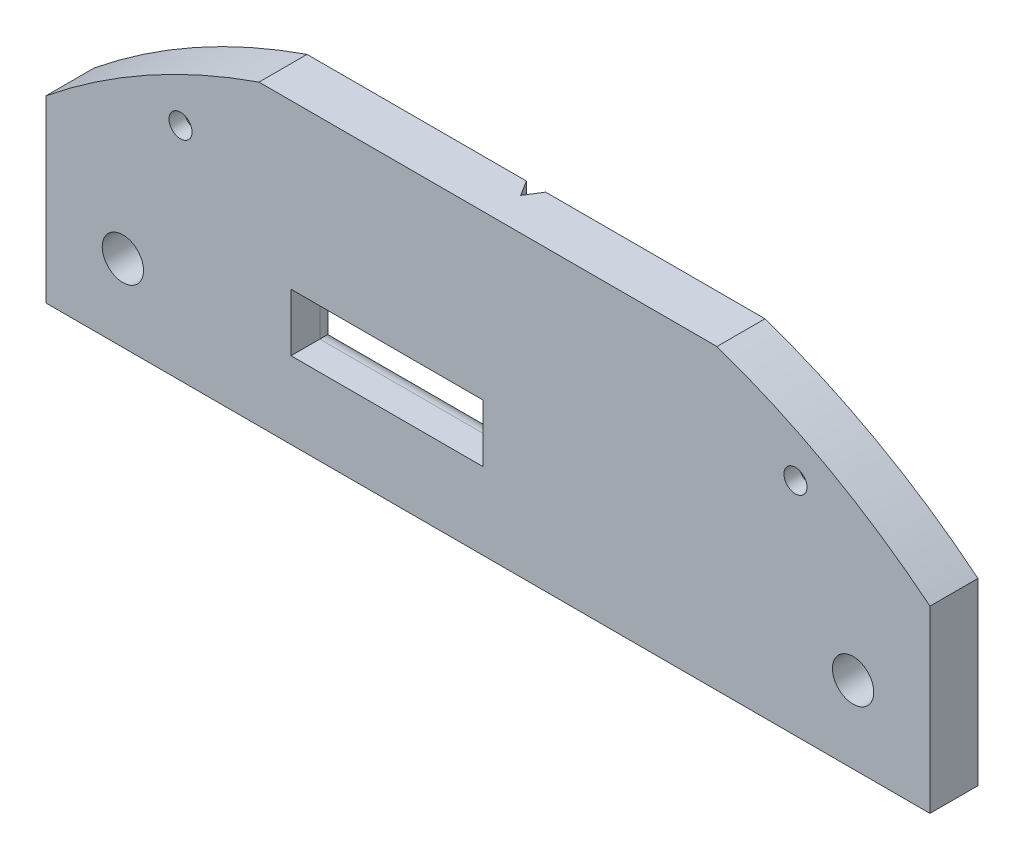
SolidWorks part; units mm, degrees
ref_plane "Front Plane" through (0, 0, 0) normal (0, 0, 1) x (1, 0, 0)
ref_plane "Top Plane" through (0, 0, 0) normal (0, 1, 0) x (1, 0, 0)
ref_plane "Right Plane" through (0, 0, 0) normal (1, 0, 0) x (0, 0, -1)
sketch "Sketch3" plane through (0, 0, 0) normal (0, 0, 1) x (1, 0, 0)
  line L1 (-46, 15.5) -> (46, 15.5)
  line L2 (-46, 15.5) -> (-46, -15.5)
  line L3 (-46, -15.5) -> (46, -15.5)
  line L4 (46, 15.5) -> (46, -15.5)
  line L5 (-46, 15.5) -> (46, -15.5) construction
  line L6 (-46, -15.5) -> (46, 15.5) construction
  point P0 (0, 0)
  dimension "D1" = 31
  dimension "D2" = 92
extrude "Boss-Extrude2" add sketch "Sketch3" along normal blind 5
sketch "Sketch4" plane through (0, 0, 5) normal (0, 0, 1) x (1, 0, 0)
  line L0 (-46, -15.5) -> (46, -15.5) construction
  circle A0 centre (0, -53.5) radius 73
  circle A1 centre (0, -53.5) radius 103
  dimension "D1" = 146
  dimension "D3" = 30
  dimension "D2" = 38
extrude "Cut-Extrude1" cut sketch "Sketch4" against normal through all
sketch "Sketch5" plane through (0, 0, 5) normal (0, 0, 1) x (1, 0, 0)
  line L1 (-46, -15.5) -> (46, -15.5) construction
  line L2 (46, -15.5) -> (46, 3.1833) construction
  line L3 (23.8328, 15.5) -> (-23.8328, 15.5) construction
  line L4 (0, -15.5) -> (0, 15.5) construction
  circle A0 centre (38, -7.5) radius 2.15
  circle A1 centre (-38, -7.5) radius 2.15
  dimension "D1" = 4.3
  dimension "D2" = 8
  dimension "D3" = 8
extrude "Cut-Extrude2" cut sketch "Sketch5" against normal through all
sketch "Sketch7" plane through (0, -15.5, 0) normal (0, -1, 0) x (1, 0, 0)
  line L0 (0, 0) -> (0, 5) construction
  line L1 (-46, 0) -> (46, 0) construction
  line L2 (-46, 5) -> (46, 5) construction
  line L3 (-1, 0) -> (0, 1.6)
  line L4 (0, 1.6) -> (1, 0)
  line L5 (1, 0) -> (-1, 0)
  dimension "D1" = 1
  dimension "D2" = 1
  dimension "D3" = 1.6
extrude "Cut-Extrude4" cut sketch "Sketch7" against normal through all
sketch "Sketch8" plane through (0, 0, 5) normal (0, 0, 1) x (1, 0, 0)
  line L0 (-46, -15.5) -> (46, -15.5) construction
  line L1 (-46, 3.1833) -> (-46, -15.5) construction
  line L2 (46, -15.5) -> (46, 3.1833) construction
  circle A0 centre (-32, 7.5) radius 1.2
  circle A1 centre (32, 7.5) radius 1.2
  dimension "D1" = 2.4
  dimension "D4" = 2.4
  dimension "D2" = 23
  dimension "D3" = 14
  dimension "D5" = 14
  dimension "D6" = 23
extrude "Cut-Extrude5" cut sketch "Sketch8" against normal through all
sketch "Sketch9" plane through (0, 0, 0) normal (0, 0, -1) x (-1, 0, 0)
  circle A0 centre (32, 7.5) radius 2.1
  circle A1 centre (-32, 7.5) radius 2.1
  dimension "D1" = 4.2
  dimension "D2" = 4.2
extrude "Cut-Extrude6" cut sketch "Sketch9" against normal blind 3.4
sketch "Sketch10" plane through (0, 0, 0) normal (0, 0, -1) x (-1, 0, 0)
  line L0 (46, -15.5) -> (1, -15.5) construction
  line L1 (0.5, -1.5) -> (20.5, -1.5)
  line L2 (0.5, -1.5) -> (0.5, -7.5)
  line L3 (0.5, -7.5) -> (20.5, -7.5)
  line L4 (20.5, -1.5) -> (20.5, -7.5)
  line L5 (0.5, -1.5) -> (20.5, -7.5) construction
  line L6 (0.5, -7.5) -> (20.5, -1.5) construction
  line L7 (46, 3.1833) -> (46, -15.5) construction
  point P0 (10.5, -4.5)
  dimension "D1" = 20
  dimension "D2" = 6
  dimension "D3" = 8
  dimension "D4" = 35.5
extrude "Cut-Extrude7" cut sketch "Sketch10" against normal through all
fillet "Fillet1" radius 2 3 edges at (-10.75, -7.5, 0) (-20.5, -4.5, 0) (-10.75, -1.5, 0)
